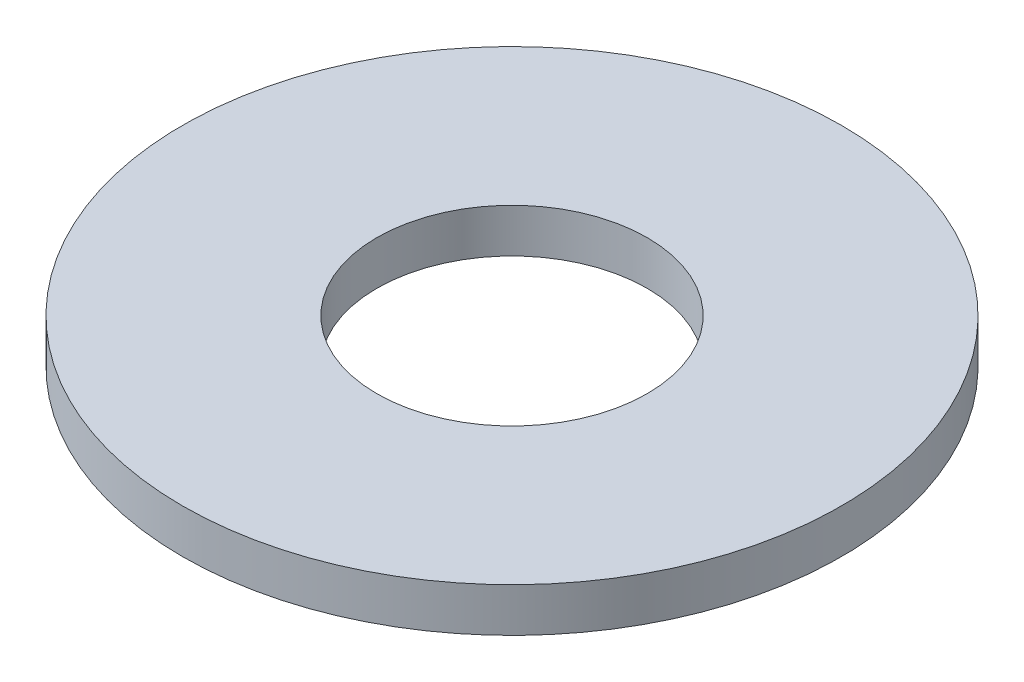
SolidWorks part; units mm, degrees
ref_plane "Front Plane" through (0, 0, 0) normal (0, 0, 1) x (1, 0, 0)
ref_plane "Top Plane" through (0, 0, 0) normal (0, 1, 0) x (1, 0, 0)
ref_plane "Right Plane" through (0, 0, 0) normal (1, 0, 0) x (0, 0, -1)
sketch "Sketch1" plane through (0, 0, 0) normal (0, 1, 0) x (1, 0, 0)
  circle A0 centre (0, 0) radius 97.5
  dimension "FLANGE_OD" = 195
extrude "Boss-Extrude1" add sketch "Sketch1" along normal blind 13
sketch "Sketch2" plane through (0, 0, 0) normal (0, 1, 0) x (1, 0, 0)
  circle A0 centre (0, 0) radius 40
  dimension "BORE_D" = 80
extrude "Cut-Extrude1" cut sketch "Sketch2" along normal through all
sketch "Sketch3" plane through (0, 13, 0) normal (0, 1, 0) x (1, 0, 0)
  circle A0 centre (0, 0) radius 33.8677 construction
  circle A1 centre (-33.8677, 0) radius 2.7099
  dimension "BOLT_D" = 5.4199
  dimension "BOLT_PCD" = 67.7354
extrude "Cut-Extrude2" cut sketch "Sketch3" against normal blind 11.4254 rebuild error yes
pattern_circular "CirPattern1" count 5 over 360 rebuild error yes
